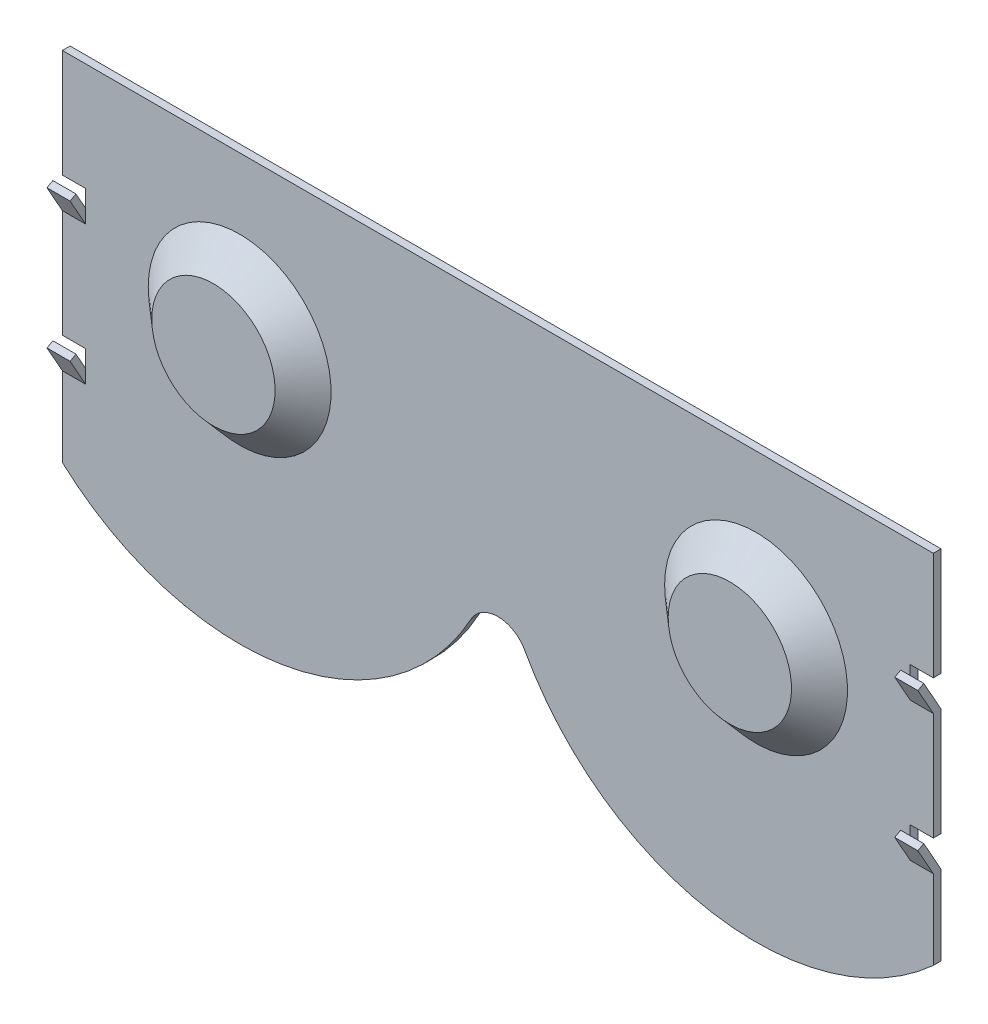
SolidWorks part; units mm, degrees
ref_plane "Plan de face" through (0, 0, 0) normal (0, 0, 1) x (1, 0, 0)
ref_plane "Plan de dessus" through (0, 0, 0) normal (0, 1, 0) x (1, 0, 0)
ref_plane "Plan de droite" through (0, 0, 0) normal (1, 0, 0) x (0, 0, -1)
sketch "Esquisse1" plane through (0, 0, 0) normal (0, 0, 1) x (1, 0, 0)
  line L0 (-28.25, 0) -> (28.25, 0)
  line L1 (28.25, 0) -> (28.25, -23.1554) construction
  line L2 (0, 0) -> (0, -40.6315) construction
  line L3 (-25.9242, -10.5) -> (28.25, -10.5) construction
  line L4 (-28.25, -7) -> (28.25, -7) construction
  line L5 (-28.25, -16) -> (28.25, -16) construction
  line L6 (-28.25, 0) -> (-28.25, -23.1554) construction
  line L7 (28.25, 0) -> (28.25, -7)
  line L8 (28.25, -7) -> (26.75, -7)
  line L10 (28.25, -9) -> (26.75, -9)
  line L11 (26.75, -7) -> (26.75, -9)
  line L12 (28.25, -16) -> (26.75, -16)
  line L14 (28.25, -18) -> (26.75, -18)
  line L15 (26.75, -16) -> (26.75, -18)
  line L16 (28.25, -9) -> (28.25, -16)
  line L17 (28.25, -18) -> (28.25, -23.1554)
  line L18 (-28.25, -18) -> (-28.25, -23.1554)
  line L19 (-28.25, -18) -> (-26.75, -18)
  line L20 (-26.75, -16) -> (-26.75, -18)
  line L21 (-28.25, -16) -> (-26.75, -16)
  line L22 (-28.25, -9) -> (-28.25, -16)
  line L23 (-28.25, -9) -> (-26.75, -9)
  line L24 (-26.75, -7) -> (-26.75, -9)
  line L25 (-28.25, -7) -> (-26.75, -7)
  line L26 (-28.25, 0) -> (-28.25, -7)
  line L27 (-23.4635, -27.6) -> (-11.2217, -27.6) construction
  arc A0 (28.25, -23.1554) -> (1.7539, -18.7175) centre (16.75, -10.5) cw
  arc A1 (1.7539, -18.7175) -> (-1.7539, -18.7175) centre (0, -19.6786) ccw
  arc A2 (-1.7539, -18.7175) -> (-28.25, -23.1554) centre (-16.75, -10.5) cw
  point P30 (-23.4635, -27.25)
  dimension "D3" = 10.5
  dimension "D6" = 2
  dimension "D10" = 2
  dimension "D11" = 33.5
  dimension "D12" = 27.6
  dimension "D1" = 56.5
  dimension "D2" = 56.5
  dimension "D4" = 7
  dimension "D5" = 16
  dimension "D7" = 2
  dimension "D8" = 1.5
extrude "Boss.-Extru.1" add sketch "Esquisse1" along normal blind 0.5
ref_plane "Plan1" through (0, -10.5, 0) normal (0, -1, 0) x (1, 0, 0)
sketch "Esquisse2" plane through (0, -10.5, 0) normal (0, -1, 0) x (1, 0, 0)
  line L0 (-16.75, 0) -> (-16.75, 2.2)
  line L2 (-16.75, 2.2) -> (-12.75, 2.2)
  line L3 (-12.75, 2.2) -> (-10.25, 0)
  line L4 (-16.75, 0) -> (-10.25, 0)
  line L7 (0, 0) -> (0, 10.798) construction
  line L8 (-28.25, 0) -> (-1.7539, 0) construction
  point P2 (0, 0)
  point P3 (-16.75, 0)
  dimension "D1" = 4
  dimension "D2" = 6.5
  dimension "D3" = 2.2
  dimension "D4" = 16.75
revolve "Révolution1" add sketch "Esquisse2" angle 360 about L0
sketch "Esquisse3" plane through (0, -10.5, 0) normal (0, -1, 0) x (1, 0, 0)
  line L0 (1.7539, 0) -> (28.25, 0) construction
  line L2 (16.75, 0) -> (16.75, 2.2)
  line L3 (16.75, 2.2) -> (20.75, 2.2)
  line L4 (20.75, 2.2) -> (23.25, 0)
  line L5 (16.75, 0) -> (23.25, 0)
  point P2 (18.0202, 0)
  dimension "D1" = 4
  dimension "D2" = 6.5
  dimension "D3" = 2.2
  dimension "D4" = 16.75
revolve "Révolution2" add sketch "Esquisse3" angle 360 about L2
sketch "Esquisse5" plane through (28.25, 0, 0) normal (1, 0, 0) x (0, 0, -1)
  line L0 (0, -18) -> (-1.1192, -16)
  line L1 (-1.1192, -16) -> (-1.5, -16.2131)
  line L2 (-1.5, -16.2131) -> (-0.5, -18)
  line L3 (-0.5, -18) -> (0, -18) construction
  line L4 (-0.5, -23.1554) -> (-0.5, -18) construction
  line L5 (-0.5, -18) -> (0, -18)
  line L6 (-0.5, -16) -> (0, -16) construction
  line L7 (0, -18) -> (0, -16) construction
  line L8 (-0.5, -9) -> (-1.5, -7.2131)
  line L9 (-1.5, -7.2131) -> (-1.1192, -7)
  line L10 (-1.1192, -7) -> (0, -9)
  line L11 (0, -9) -> (-0.5, -9)
  line L12 (-0.5, -7) -> (0, -7) construction
  point P3 (0, 0)
  point P18 (1.5796, -6.8726)
  point P19 (0, -9)
  point P21 (-1.6418, -7.4009)
  dimension "D1" = 1.5
extrude "Boss.-Extru.2" add sketch "Esquisse5" against normal blind 1.5
extrude "Boss.-Extru.3" add sketch "Esquisse5<2>" against normal blind 1.5 from surface starting at face at (-26.75, -17, 0.25)
sketch "Esquisse5<2>" plane through (28.25, 0, 0) normal (1, 0, 0) x (0, 0, -1) same geometry as "Esquisse5"
